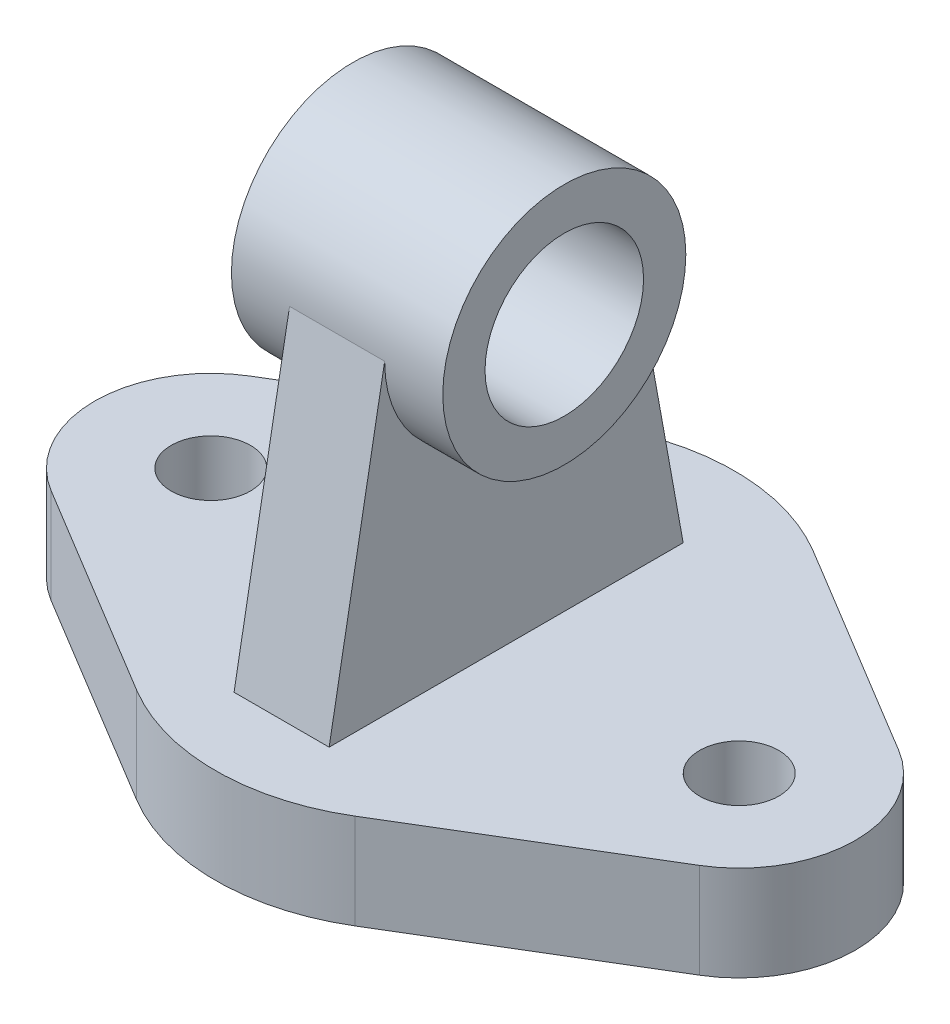
SolidWorks part; units mm, degrees
ref_plane "Front" through (0, 0, 0) normal (0, 0, 1) x (1, 0, 0)
ref_plane "Top" through (0, 0, 0) normal (0, 1, 0) x (1, 0, 0)
ref_plane "Right" through (0, 0, 0) normal (1, 0, 0) x (0, 0, -1)
sketch "Sketch2" plane through (0, 0, 0) normal (0, 1, 0) x (1, 0, 0)
  line L0 (-50.2847, 19.3582) -> (-9.5794, 43.9028)
  line L1 (31.7304, 43.9028) -> (72.4357, 19.3582)
  line L2 (72.4357, -18.3218) -> (31.7304, -42.8665)
  line L3 (-9.5794, -42.8665) -> (-50.2847, -18.3218)
  line L4 (-81.5293, 0.5182) -> (103.6803, 0.5182) construction
  line L5 (11.0755, 56.3574) -> (11.0755, -55.3211) construction
  arc A0 (31.7304, -42.8665) -> (-9.5794, -42.8665) centre (11.0755, -8.6119) cw
  arc A1 (-9.5794, 43.9028) -> (31.7304, 43.9028) centre (11.0755, 9.6483) cw
  arc A2 (-50.2847, 19.3582) -> (-50.2847, -18.3218) centre (-38.9245, 0.5182) ccw
  arc A3 (72.4357, 19.3582) -> (72.4357, -18.3218) centre (61.0755, 0.5182) cw
  circle A4 centre (-38.9245, 0.5182) radius 7.5
  circle A5 centre (61.0755, 0.5182) radius 7.5
  point P10 (-50.2847, -18.3218)
  dimension "D1" = 40
  dimension "D2" = 22
  dimension "D3" = 15
  dimension "D5" = 100
extrude "Boss-Extrude1" add sketch "Sketch2" along normal blind 18
sketch "Sketch6" plane through (0, 0, 0) normal (1, 0, 0) x (0, 0, -1)
  line L0 (-34.0071, 18) -> (32.9929, 18) construction
  line L1 (-42.8665, 18) -> (-18.3218, 18) construction
  line L2 (19.3582, 18) -> (43.9028, 18) construction
  line L3 (0, 0) -> (-0.5071, 18) construction
  line L4 (-0.5071, 18) -> (-0.5071, 76) construction
  line L5 (-34.0071, 18) -> (-23.5071, 76)
  line L6 (22.4929, 76) -> (32.9929, 18)
  line L7 (32.9929, 18) -> (-34.0071, 18)
  arc A0 (22.4929, 76) -> (-23.5071, 76) centre (-0.5071, 76) ccw
  circle A1 centre (-0.5071, 76) radius 15
  dimension "D3" = 46
  dimension "D4" = 30
  dimension "D1" = 67
  dimension "D2" = 58
extrude "Boss-Extrude2" add sketch "Sketch6" along normal blind 18
sketch "Sketch7" plane through (18, 0, 0) normal (1, 0, 0) x (0, 0, -1)
  circle A0 centre (-0.5071, 76) radius 15
  circle A1 centre (-0.5071, 76) radius 23
  dimension "D1" = 30
  dimension "D2" = 46
extrude "Boss-Extrude3" add sketch "Sketch7" along normal blind 11
sketch "Sketch8" plane through (0, 0, 0) normal (-1, 0, 0) x (0, 0, 1)
  circle A0 centre (0.5071, 76) radius 15
  circle A1 centre (0.5071, 76) radius 23
extrude "Boss-Extrude4" add sketch "Sketch8" along normal blind 11
